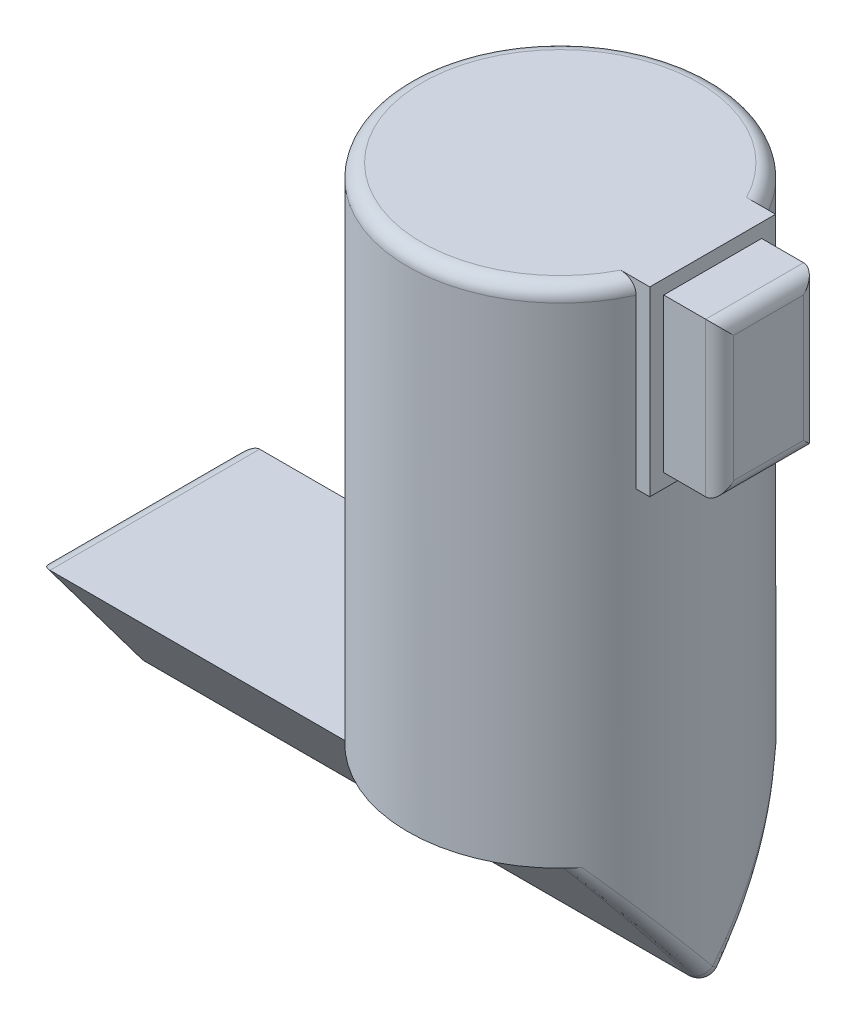
SolidWorks part; units mm, degrees
material "6063-T5"
ref_plane "Front" through (0, 0, 0) normal (0, 0, 1) x (1, 0, 0)
ref_plane "Top" through (0, 0, 0) normal (0, 1, 0) x (1, 0, 0)
ref_plane "Right" through (0, 0, 0) normal (1, 0, 0) x (0, 0, -1)
sketch "Sketch1" plane through (0, 0, 0) normal (0, 1, 0) x (1, 0, 0)
  circle A0 centre (0, 0) radius 2.7686
  dimension "D1" = 5.5372
extrude "Boss-Extrude1" add sketch "Sketch1" along normal blind 9.144
sketch "Sketch2" plane through (0, 9.144, 0) normal (0, 1, 0) x (1, 0, 0)
  line L0 (2.7686, 1.143) -> (2.7686, -1.143) construction
  line L4 (-1.1274, 1.143) -> (-1.1274, -1.143)
  line L6 (3.7846, 1.143) -> (3.7846, -1.143)
  line L7 (-1.1274, 1.143) -> (3.7846, 1.143)
  line L8 (-1.1274, -1.143) -> (3.7846, -1.143)
  line L9 (0, 0) -> (4.8619, 0) construction
  point P3 (2.7686, 0)
  dimension "D1" = 2.286
  dimension "D2" = 1.016
  dimension "D4" = 2.7686
extrude "Boss-Extrude2" add sketch "Sketch2" against normal blind 3.302
sketch "Sketch3" plane through (3.7846, 0, 0) normal (1, 0, 0) x (0, 0, -1)
  line L1 (-0.889, 6.096) -> (0.889, 6.096)
  line L2 (-0.889, 6.096) -> (-0.889, 8.89)
  line L3 (-0.889, 8.89) -> (0.889, 8.89)
  line L4 (0.889, 6.096) -> (0.889, 8.89)
  line L5 (-1.143, 9.144) -> (1.143, 9.144)
  line L6 (-1.143, 9.144) -> (-1.143, 5.842)
  line L7 (-1.143, 5.842) -> (1.143, 5.842)
  line L8 (1.143, 9.144) -> (1.143, 5.842)
  dimension "D1" = 0.254
  dimension "D2" = 0.254
  dimension "D3" = 0.254
  dimension "D4" = 0.254
extrude "Cut-Extrude1" cut sketch "Sketch3" against normal blind 1.016
sketch "Sketch4" plane through (0, 0, 0) normal (1, 0, 0) x (0, 0, -1)
  line L0 (-1.905, 0) -> (1.905, 0)
  line L1 (0, 0) -> (0, -2.54) construction
  line L2 (-1.905, 0) -> (0, -2.54)
  line L3 (0, -2.54) -> (1.905, 0)
  point P4 (0, 0)
  dimension "D1" = 3.81
  dimension "D2" = 2.54
extrude "Boss-Extrude3" add sketch "Sketch4" along normal blind 3.937 and the other way blind 7.62
sketch "Sketch5" plane through (0, 0, 0) normal (0, -1, 0) x (1, 0, 0)
  line L0 (2.009, 1.905) -> (3.937, 1.905)
  line L1 (3.937, 1.905) -> (3.937, -1.905)
  line L2 (3.937, -1.905) -> (2.009, -1.905)
  arc A0 (2.009, -1.905) -> (2.009, 1.905) centre (0, 0) ccw
  arc A1 (2.009, 1.905) -> (-2.009, 1.905) centre (0, 0) ccw construction
extrude "Cut-Extrude2" cut sketch "Sketch5" along normal through all
fillet "Fillet2" radius 0.254 11 edges at (-2.4257, -2.54, 0) (-7.62, 0, 0) (-7.62, -1.27, 0.9525) (-7.62, -1.27, -0.9525) (-2.7686, 9.144, 0) (3.7846, 6.096, 0) (3.7846, 7.493, -0.889) (3.7846, 7.493, 0.889) (3.7846, 8.89, 0) (2.5717, -1.1728, -1.0254) (2.5717, -1.1728, 1.0254)
